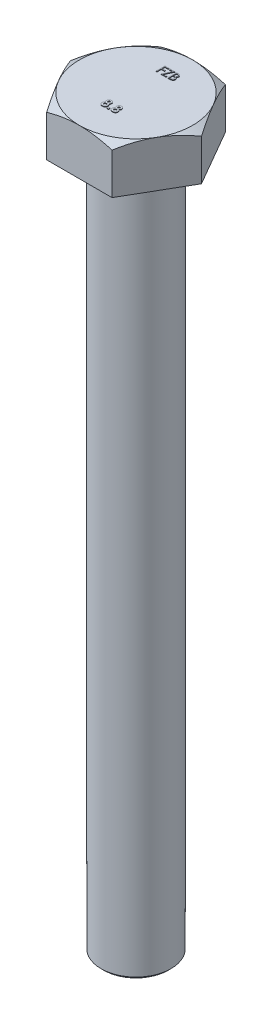
SolidWorks part; units mm, degrees
ref_plane "Front Plane" through (0, 0, 0) normal (0, 0, 1) x (1, 0, 0)
ref_plane "Top Plane" through (0, 0, 0) normal (0, 1, 0) x (1, 0, 0)
ref_plane "Right Plane" through (0, 0, 0) normal (1, 0, 0) x (0, 0, -1)
sketch "Sketch2" plane through (0, 0, 0) normal (0, 1, 0) x (1, 0, 0)
  line L1 (7.5056, 0) -> (3.7528, 6.5)
  line L2 (3.7528, 6.5) -> (-3.7528, 6.5)
  line L3 (-3.7528, 6.5) -> (-7.5056, 0)
  line L4 (-7.5056, 0) -> (-3.7528, -6.5)
  line L5 (-3.7528, -6.5) -> (3.7528, -6.5)
  line L6 (3.7528, -6.5) -> (7.5056, 0)
  circle A0 centre (0, 0) radius 6.5 construction
  dimension "s" = 13
extrude "Boss-Extrude1" add sketch "Sketch2" against normal blind 5.3
sketch "Sketch4" plane through (0, -5.3, 0) normal (0, -1, 0) x (1, 0, 0)
  circle A0 centre (0, 0) radius 4
  dimension "d" = 8
extrude "Boss-Extrude3" add sketch "Sketch4" along normal blind 80
chamfer "Chamfer2" distance 0.3 angle 45 1 edges at (0, -85.3, -4)
sketch "Sketch6" plane through (0, 0, 0) normal (0, 0, 1) x (1, 0, 0)
  line L6 (-6.5, 0) -> (6.5, 0) construction
  line L7 (0, 0) -> (0, 3.7528) construction
  line L8 (0, 3.7528) -> (-6.5, 0) construction
  line L9 (-6.5, 0) -> (-22.5167, -9.2472)
  line L10 (-22.5167, -9.2472) -> (-22.5167, 3.7528)
  line L11 (-22.5167, 3.7528) -> (-6.5, 3.7528)
  line L12 (-6.5, 0) -> (-6.5, 3.7528)
  line L13 (-6.5, 3.7528) -> (0, 3.7528) construction
  point P2 (0, 0)
  dimension "s" = 13
  dimension "D2" = 30
revolve "Cut-Revolve4" cut sketch "Sketch6" angle 360 about L7
sketch "Sketch7" plane through (0, -85.3, 0) normal (0, -1, 0) x (1, 0, 0)
  circle A2 centre (0, 0) radius 3.7
  circle A3 centre (0, 0) radius 3.7
  dimension "D1" = 0
curve "Helix/Spiral1" pitch 1.25 height 25 turns 20 parameters "ganga"=25, "stigning"=1.25
sketch "Sketch9" plane through (0, 0, 0) normal (1, 0, 0) x (0, 0, -1)
  line L0 (-4, -84.7922) -> (-4, -85.8078)
  line L1 (-4, -85.8078) -> (-3.3235, -85.4172)
  line L2 (-4, -84.7922) -> (-3.3235, -85.1828)
  line L3 (-3.3235, -85.1828) -> (-3.1205, -85.3) construction
  line L4 (-3.3235, -85.1828) -> (-3.3235, -85.4172) construction
  line L5 (4, -85) -> (4, -5.3) construction
  line L6 (-3.1205, -85.3) -> (-3.3235, -85.4172) construction
  line L8 (7.15, 0) -> (-7.15, 0) construction
  line L9 (-3.7, -85.3) -> (3.7, -85.3) construction
  line L10 (-3.7, -85.3) -> (3.7, -85.3) construction
  line L11 (0, 0) -> (0, -85.3) construction
  line L12 (4, -85) -> (4, -5.3) construction
  line L13 (4, -85) -> (4, -85.3) construction
  line L14 (4, -85.3) -> (3.7, -85.3) construction
  line L15 (-4, -5.3) -> (-4, -85) construction
  line L16 (-4, -5.3) -> (-4, -85) construction
  line L17 (-4, -85) -> (-4, -85.3) construction
  line L18 (-4, -85.3) -> (-3.7, -85.3) construction
  spline S0 degree 3 poles (-3.3235, -85.1828) (-3.3074, -85.1921) (-3.2038, -85.2997) (-3.3084, -85.4085) (-3.3235, -85.4172) knots 0 0 0 0 0.5 1 1 1 1
  point P3 (-4, -85.3)
  point P13 (-3.3235, -85.3)
  dimension "D3" = 0.2344
  dimension "D1" = 60
  dimension "D_1" = 3.3235
  dimension "D4" = 0.203
  dimension "D5" = 0.1353
sweep "Cut-Sweep4" [suppressed] cut profiles "Sketch9" path "Helix/Spiral1"
sketch "Sketch11" plane through (0, 0, 0) normal (0, 1, 0) x (1, 0, 0)
  line L1 (-5.6292, 3.25) -> (5.6292, 3.25) construction
  line L2 (-5.6292, -3.25) -> (5.6292, -3.25) construction
  text T0 "<b>8.8</b>" font "Century Gothic" height 1
  text T1 "FZB" font "Century Gothic" height 1
extrude "Boss-Extrude5" add sketch "Sketch11" along normal blind 0.05
equation "\"D3@Sketch9\" =  ( \"stigning@Helix/Spiral1\" )  / 5.33333"
equation "\"D5@Sketch9\" = ( \"D4@Sketch9\" * 2)/3"
